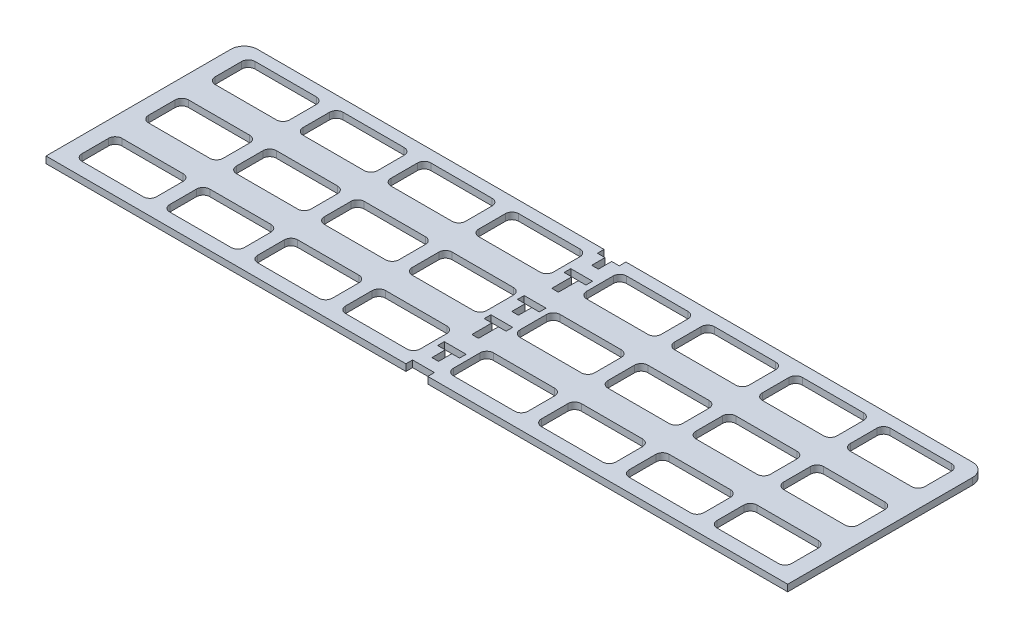
SolidWorks part; units mm, degrees
material "Balsa"
ref_plane "Front Plane" through (0, 0, 0) normal (0, 0, 1) x (1, 0, 0)
ref_plane "Top Plane" through (0, 0, 0) normal (0, 1, 0) x (1, 0, 0)
ref_plane "Right Plane" through (0, 0, 0) normal (1, 0, 0) x (0, 0, -1)
sketch "Sketch1" plane through (0, 0, 0) normal (0, 1, 0) x (1, 0, 0)
  line L0 (0, 0) -> (350.52, 0)
  line L1 (337.82, 188.976) -> (0, 188.976)
  line L3 (350.52, 0) -> (350.52, 176.276)
  line L4 (0, 188.976) -> (0, 169.926)
  line L5 (0, 169.926) -> (-3.175, 169.926)
  line L6 (-3.175, 169.926) -> (-3.175, 150.876)
  line L7 (-3.175, 150.876) -> (0, 150.876)
  line L8 (0, 150.876) -> (0, 131.826)
  line L9 (0, 131.826) -> (-3.175, 131.826)
  line L10 (-3.175, 131.826) -> (-3.175, 112.776)
  line L11 (-3.175, 112.776) -> (0, 112.776)
  line L12 (0, 112.776) -> (0, 93.726)
  line L13 (0, 93.726) -> (-3.175, 93.726)
  line L14 (-3.175, 93.726) -> (-3.175, 74.676)
  line L15 (-3.175, 74.676) -> (0, 74.676)
  line L16 (0, 74.676) -> (0, 55.626)
  line L17 (0, 55.626) -> (-3.175, 55.626)
  line L18 (-3.175, 55.626) -> (-3.175, 36.576)
  line L19 (-3.175, 36.576) -> (0, 36.576)
  line L20 (0, 36.576) -> (0, 17.526)
  line L21 (0, 17.526) -> (-3.175, 17.526)
  line L22 (-3.175, 17.526) -> (-3.175, 0)
  line L23 (-3.175, 0) -> (0, 0)
  arc A0 (337.82, 188.976) -> (350.52, 176.276) centre (337.82, 176.276) cw
  point P7 (350.52, 188.976)
  dimension "D4" = 12.7
  dimension "D2" = 350.52
  dimension "D3" = 188.976
  dimension "D5" = 19.05
  dimension "D6" = 19.05
  dimension "D7" = 3.175
  dimension "D8" = 19.05
  dimension "D9" = 19.05
  dimension "D10" = 19.05
  dimension "D11" = 19.05
  dimension "D12" = 19.05
  dimension "D13" = 19.05
  dimension "D14" = 3.175
  dimension "D15" = 3.175
  dimension "D16" = 3.175
  dimension "D17" = 3.175
  dimension "D18" = 337.82
  dimension "D19" = 3.175
  dimension "D20" = 19.05
  dimension "D21" = 3.175
  dimension "D22" = 176.276
  dimension "D23" = 3.175
extrude "Boss-Extrude1" add sketch "Sketch1" along normal blind 6.35
sketch "Sketch2" plane through (0, 6.35, 0) normal (0, 1, 0) x (1, 0, 0)
  line L68 (264.16, 19.05) -> (264.16, 44.45)
  line L69 (270.51, 12.7) -> (328.93, 12.7)
  line L70 (335.28, 19.05) -> (335.28, 44.45)
  line L71 (270.51, 50.8) -> (328.93, 50.8)
  line L72 (264.16, 82.55) -> (264.16, 107.95)
  line L73 (270.51, 76.2) -> (328.93, 76.2)
  line L74 (335.28, 82.55) -> (335.28, 107.95)
  line L76 (96.52, 19.05) -> (96.52, 44.45)
  line L77 (270.51, 114.3) -> (328.93, 114.3)
  line L78 (264.16, 146.05) -> (264.16, 171.45)
  line L79 (270.51, 139.7) -> (328.93, 139.7)
  line L80 (335.28, 146.05) -> (335.28, 171.45)
  line L81 (270.51, 177.8) -> (328.93, 177.8)
  line L91 (19.05, 12.7) -> (77.47, 12.7)
  line L92 (12.7, 19.05) -> (12.7, 44.45)
  line L93 (19.05, 50.8) -> (77.47, 50.8)
  line L94 (83.82, 19.05) -> (83.82, 44.45)
  line L95 (102.87, 12.7) -> (161.29, 12.7)
  line L96 (167.64, 19.05) -> (167.64, 44.45)
  line L97 (102.87, 50.8) -> (161.29, 50.8)
  line L98 (180.34, 19.05) -> (180.34, 44.45)
  line L99 (186.69, 12.7) -> (245.11, 12.7)
  line L100 (251.46, 19.05) -> (251.46, 44.45)
  line L101 (186.69, 50.8) -> (245.11, 50.8)
  line L102 (96.52, 82.55) -> (96.52, 107.95)
  line L103 (102.87, 76.2) -> (161.29, 76.2)
  line L104 (167.64, 82.55) -> (167.64, 107.95)
  line L105 (102.87, 114.3) -> (161.29, 114.3)
  line L106 (180.34, 82.55) -> (180.34, 107.95)
  line L107 (186.69, 76.2) -> (245.11, 76.2)
  line L108 (251.46, 82.55) -> (251.46, 107.95)
  line L109 (186.69, 114.3) -> (245.11, 114.3)
  line L110 (96.52, 146.05) -> (96.52, 171.45)
  line L111 (102.87, 139.7) -> (161.29, 139.7)
  line L112 (167.64, 146.05) -> (167.64, 171.45)
  line L113 (102.87, 177.8) -> (161.29, 177.8)
  line L114 (180.34, 146.05) -> (180.34, 171.45)
  line L115 (186.69, 139.7) -> (245.11, 139.7)
  line L116 (251.46, 146.05) -> (251.46, 171.45)
  line L117 (186.69, 177.8) -> (245.11, 177.8)
  line L118 (12.7, 82.55) -> (12.7, 107.95)
  line L119 (19.05, 76.2) -> (77.47, 76.2)
  line L120 (83.82, 82.55) -> (83.82, 107.95)
  line L121 (19.05, 114.3) -> (77.47, 114.3)
  line L122 (12.7, 146.05) -> (12.7, 171.45)
  line L123 (19.05, 139.7) -> (77.47, 139.7)
  line L124 (83.82, 146.05) -> (83.82, 171.45)
  line L125 (19.05, 177.8) -> (77.47, 177.8)
  line L126 (12.7, 19.05) -> (12.7, 82.55) construction
  arc A0 (77.47, 12.7) -> (83.82, 19.05) centre (77.47, 19.05) ccw
  arc A1 (19.05, 12.7) -> (12.7, 19.05) centre (19.05, 19.05) cw
  arc A2 (12.7, 44.45) -> (19.05, 50.8) centre (19.05, 44.45) cw
  arc A3 (77.47, 50.8) -> (83.82, 44.45) centre (77.47, 44.45) cw
  arc A4 (96.52, 44.45) -> (102.87, 50.8) centre (102.87, 44.45) cw
  arc A5 (102.87, 12.7) -> (96.52, 19.05) centre (102.87, 19.05) cw
  arc A6 (161.29, 12.7) -> (167.64, 19.05) centre (161.29, 19.05) ccw
  arc A7 (161.29, 50.8) -> (167.64, 44.45) centre (161.29, 44.45) cw
  arc A8 (180.34, 44.45) -> (186.69, 50.8) centre (186.69, 44.45) cw
  arc A9 (186.69, 12.7) -> (180.34, 19.05) centre (186.69, 19.05) cw
  arc A10 (245.11, 12.7) -> (251.46, 19.05) centre (245.11, 19.05) ccw
  arc A11 (245.11, 50.8) -> (251.46, 44.45) centre (245.11, 44.45) cw
  arc A12 (96.52, 107.95) -> (102.87, 114.3) centre (102.87, 107.95) cw
  arc A13 (102.87, 76.2) -> (96.52, 82.55) centre (102.87, 82.55) cw
  arc A14 (161.29, 76.2) -> (167.64, 82.55) centre (161.29, 82.55) ccw
  arc A15 (161.29, 114.3) -> (167.64, 107.95) centre (161.29, 107.95) cw
  arc A16 (180.34, 107.95) -> (186.69, 114.3) centre (186.69, 107.95) cw
  arc A17 (186.69, 76.2) -> (180.34, 82.55) centre (186.69, 82.55) cw
  arc A18 (245.11, 76.2) -> (251.46, 82.55) centre (245.11, 82.55) ccw
  arc A19 (245.11, 114.3) -> (251.46, 107.95) centre (245.11, 107.95) cw
  arc A20 (96.52, 171.45) -> (102.87, 177.8) centre (102.87, 171.45) cw
  arc A21 (102.87, 139.7) -> (96.52, 146.05) centre (102.87, 146.05) cw
  arc A22 (161.29, 139.7) -> (167.64, 146.05) centre (161.29, 146.05) ccw
  arc A23 (161.29, 177.8) -> (167.64, 171.45) centre (161.29, 171.45) cw
  arc A24 (180.34, 171.45) -> (186.69, 177.8) centre (186.69, 171.45) cw
  arc A25 (186.69, 139.7) -> (180.34, 146.05) centre (186.69, 146.05) cw
  arc A26 (245.11, 139.7) -> (251.46, 146.05) centre (245.11, 146.05) ccw
  arc A27 (245.11, 177.8) -> (251.46, 171.45) centre (245.11, 171.45) cw
  arc A28 (12.7, 107.95) -> (19.05, 114.3) centre (19.05, 107.95) cw
  arc A29 (19.05, 76.2) -> (12.7, 82.55) centre (19.05, 82.55) cw
  arc A30 (77.47, 76.2) -> (83.82, 82.55) centre (77.47, 82.55) ccw
  arc A31 (77.47, 114.3) -> (83.82, 107.95) centre (77.47, 107.95) cw
  arc A32 (12.7, 171.45) -> (19.05, 177.8) centre (19.05, 171.45) cw
  arc A33 (19.05, 139.7) -> (12.7, 146.05) centre (19.05, 146.05) cw
  arc A34 (77.47, 139.7) -> (83.82, 146.05) centre (77.47, 146.05) ccw
  arc A35 (77.47, 177.8) -> (83.82, 171.45) centre (77.47, 171.45) cw
  arc A36 (264.16, 44.45) -> (270.51, 50.8) centre (270.51, 44.45) cw
  arc A37 (270.51, 12.7) -> (264.16, 19.05) centre (270.51, 19.05) cw
  arc A38 (328.93, 12.7) -> (335.28, 19.05) centre (328.93, 19.05) ccw
  arc A39 (328.93, 50.8) -> (335.28, 44.45) centre (328.93, 44.45) cw
  arc A40 (264.16, 107.95) -> (270.51, 114.3) centre (270.51, 107.95) cw
  arc A41 (270.51, 76.2) -> (264.16, 82.55) centre (270.51, 82.55) cw
  arc A42 (328.93, 76.2) -> (335.28, 82.55) centre (328.93, 82.55) ccw
  arc A43 (328.93, 114.3) -> (335.28, 107.95) centre (328.93, 107.95) cw
  arc A44 (264.16, 171.45) -> (270.51, 177.8) centre (270.51, 171.45) cw
  arc A45 (270.51, 139.7) -> (264.16, 146.05) centre (270.51, 146.05) cw
  arc A46 (328.93, 139.7) -> (335.28, 146.05) centre (328.93, 146.05) ccw
  arc A47 (328.93, 177.8) -> (335.28, 171.45) centre (328.93, 171.45) cw
  point P10 (83.82, 12.7)
  point P13 (12.7, 12.7)
  point P16 (12.7, 50.8)
  point P19 (96.52, 31.75)
  dimension "D7" = 3
  dimension "D5" = 6.35
  dimension "D2" = 71.12
  dimension "D3" = 12.7
  dimension "D4" = 38.1
  dimension "D8" = 63.5
  dimension "D9" = 25.4
  dimension "D10" = 12.7
  dimension "D11" = 12.7
  dimension "D6" = 4
extrude "Cut-Extrude1" cut sketch "Sketch2" against normal up to surface (6.35 mm away) up to face at (43.9018, 0, -97.562)
mirror "Mirror1" about plane through (-3.175, 6.35, -93.726) normal (1, 0, 0) of "Cut-Extrude1", "Boss-Extrude1"
sketch "Sketch3" plane through (0, 6.35, 0) normal (0, 1, 0) x (1, 0, 0)
  line L8 (-13.589, 182.626) -> (7.239, 182.626)
  line L9 (-13.589, 182.626) -> (-13.589, 188.976)
  line L10 (-13.589, 188.976) -> (7.239, 188.976)
  line L11 (7.239, 182.626) -> (7.239, 188.976)
  line L12 (-13.589, 150.876) -> (7.239, 150.876)
  line L13 (-13.589, 150.876) -> (-13.589, 157.226)
  line L14 (-13.589, 157.226) -> (7.239, 157.226)
  line L15 (7.239, 150.876) -> (7.239, 157.226)
  line L16 (-13.589, 30.226) -> (7.239, 30.226)
  line L17 (-13.589, 30.226) -> (-13.589, 36.576)
  line L18 (-13.589, 36.576) -> (7.239, 36.576)
  line L19 (7.239, 30.226) -> (7.239, 36.576)
  line L20 (-13.589, 0) -> (7.239, 0)
  line L21 (-13.589, 0) -> (-13.589, 6.35)
  line L22 (-13.589, 6.35) -> (7.239, 6.35)
  line L23 (7.239, 0) -> (7.239, 6.35)
  line L24 (-13.589, 106.426) -> (7.239, 106.426)
  line L25 (-13.589, 106.426) -> (-13.589, 112.776)
  line L26 (-13.589, 112.776) -> (7.239, 112.776)
  line L27 (7.239, 106.426) -> (7.239, 112.776)
  line L28 (-13.589, 74.676) -> (7.239, 74.676)
  line L29 (-13.589, 74.676) -> (-13.589, 81.026)
  line L30 (-13.589, 81.026) -> (7.239, 81.026)
  line L31 (7.239, 74.676) -> (7.239, 81.026)
  line L32 (0, 169.926) -> (-6.35, 169.926) construction
  line L33 (337.82, 188.976) -> (0, 188.976) construction
  line L35 (-6.35, 150.876) -> (0, 150.876) construction
  line L36 (-6.35, 112.776) -> (0, 112.776) construction
  line L37 (-6.35, 74.676) -> (0, 74.676) construction
  line L38 (-6.35, 36.576) -> (0, 36.576) construction
  line L39 (-356.87, 0) -> (350.52, 0) construction
  point P0 (-3.175, 169.926)
  point P1 (-3.175, 188.976)
  point P4 (-3.175, 157.226)
  point P5 (-3.175, 112.776)
  point P6 (-3.175, 81.026)
  point P7 (-3.175, 36.576)
  point P24 (-3.175, 6.35)
  point P33 (0, 0)
  dimension "D5" = 20.828
  dimension "D6" = 6.35
  dimension "D7" = 20.828
  dimension "D8" = 6.35
  dimension "D9" = 20.828
  dimension "D10" = 6.35
  dimension "D11" = 20.828
  dimension "D12" = 6.35
  dimension "D13" = 20.828
  dimension "D14" = 6.35
  dimension "D15" = 20.828
  dimension "D16" = 6.35
extrude "Cut-Extrude2" cut sketch "Sketch3" against normal through all
